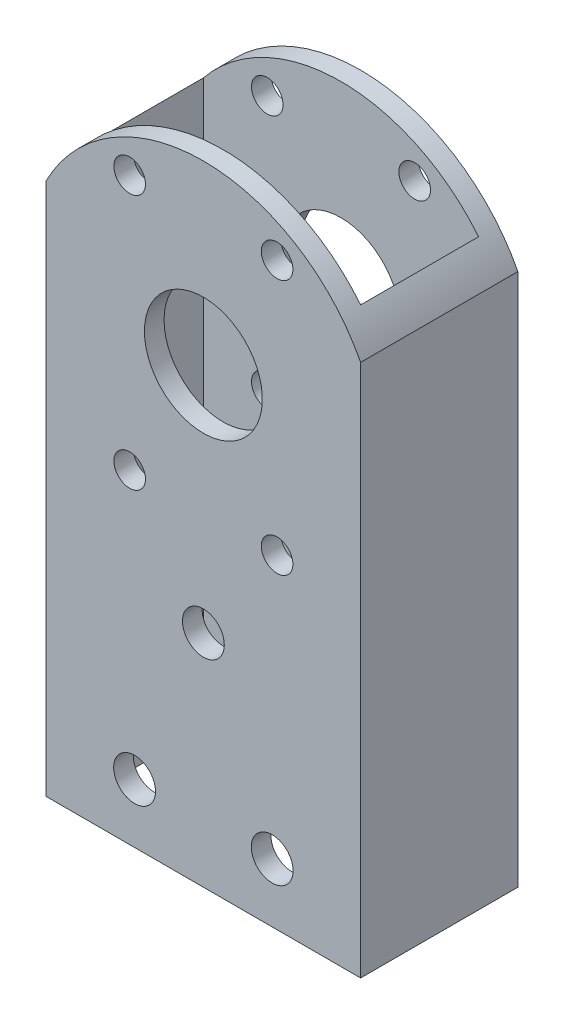
SolidWorks part; units mm, degrees
material "6061-T6 (SS)"
ref_plane "Front" through (0, 0, 0) normal (0, 0, 1) x (1, 0, 0)
ref_plane "Top" through (0, 0, 0) normal (0, 1, 0) x (1, 0, 0)
ref_plane "Right" through (0, 0, 0) normal (1, 0, 0) x (0, 0, -1)
sketch "Sketch1" plane through (0, 0, 0) normal (0, 1, 0) x (1, 0, 0)
  line L1 (-25.4, -12.7) -> (25.4, -12.7)
  line L2 (-25.4, -12.7) -> (-25.4, 12.7)
  line L3 (-25.4, 12.7) -> (25.4, 12.7)
  line L4 (25.4, -12.7) -> (25.4, 12.7)
  line L5 (-25.4, -12.7) -> (25.4, 12.7) construction
  line L6 (-25.4, 12.7) -> (25.4, -12.7) construction
  point P0 (0, 0)
  dimension "D1" = 25.4
  dimension "D2" = 50.8
extrude "Extrude-Thin1" add sketch "Sketch1" along normal blind 101.6 thin thin type one direction reverse wall 3.175
sketch "Sketch2" plane through (0, 0, -12.7) normal (0, 0, -1) x (-1, 0, 0)
  line L0 (0, 101.6) -> (0, 69.85)
  line L1 (-25.4, 101.6) -> (25.4, 101.6) construction
  line L3 (0, 60.325) -> (0, 79.375) construction
  circle A1 centre (0, 69.85) radius 23.8125
  circle A3 centre (0, 69.85) radius 9.525
  point P12 (0, 69.85)
  dimension "D1" = 19.05
  dimension "D3" = 47.625
  dimension "D2" = 31.75
hole_wizard "#10 Clearance Hole1" positions "Sketch5" profile "Sketch6" hole size "#10" standard "ANSI Inch" end condition through all
sketch "Sketch5" plane through (0, 0, -12.7) normal (0, 0, -1) x (-1, 0, 0)
  line L0 (0, 101.6) -> (0, 73.025)
  line L1 (-25.4, 101.6) -> (25.4, 101.6) construction
  line L3 (-11.9063, 93.6472) -> (11.9063, 93.6472)
  line L4 (-11.9063, 93.6472) -> (-11.9063, 52.4028)
  line L5 (-11.9063, 52.4028) -> (11.9063, 52.4028)
  line L6 (11.9063, 93.6472) -> (11.9063, 52.4028)
  circle A0 centre (0, 73.025) radius 23.8125
  point P21 (-11.9063, 93.6472)
  point P22 (11.9063, 93.6472)
  point P24 (11.9063, 52.4028)
  point P25 (-11.9063, 52.4028)
  dimension "D1" = 47.625
  dimension "D2" = 28.575
  dimension "D3" = 23.8125
sketch "Sketch6" plane through (11.9063, 52.4028, -12.7) normal (1, 0, 0) x (0, 1, 0)
  line L0 (0, 0) -> (0, 25.4)
  line L1 (0, 25.4) -> (2.5527, 25.4)
  line L2 (2.5527, 25.4) -> (2.5527, 0)
  line L5 (2.5527, 0) -> (0, 0)
  line L11 (0, -6.35) -> (0, 107.95) construction
  dimension "Thru Hole Dia." = 5.1054
  dimension "Thru Hole Depth" = 25.4
sketch "Sketch7" plane through (0, 0, -12.7) normal (0, 0, -1) x (-1, 0, 0)
  line L0 (-11.9063, 93.6472) -> (11.9063, 52.4028) construction
  circle A1 centre (0, 73.025) radius 9.525
  point P9 (0, 73.025)
  dimension "D1" = 19.05
extrude "Cut-Extrude2" cut sketch "Sketch7" against normal through all both
hole_wizard "1/4 Clearance Hole2" positions "Sketch8" profile "Sketch9" hole size "1/4" standard "ANSI Inch" end condition through all
sketch "Sketch8" plane through (0, 0, 12.7) normal (0, 0, 1) x (1, 0, 0)
  line L2 (-25.4, 101.6) -> (-25.4, 0) construction
  line L4 (-25.4, 0) -> (25.4, 0) construction
  point P0 (-11.1125, 9.525)
  point P2 (11.1125, 9.525)
  point P14 (-109.1715, 68.7854)
  dimension "D1" = 22.225
  dimension "D2" = 14.2875
  dimension "D3" = 9.525
sketch "Sketch9" plane through (-11.1125, 9.525, 12.7) normal (1, 0, 0) x (0, -1, 0)
  line L0 (0, 0) -> (0, 25.4)
  line L1 (0, 25.4) -> (3.3782, 25.4)
  line L2 (3.3782, 25.4) -> (3.3782, 0)
  line L5 (3.3782, 0) -> (0, 0)
  line L11 (0, -6.35) -> (0, 107.95) construction
  dimension "Thru Hole Dia." = 6.7564
  dimension "Thru Hole Depth" = 25.4
sketch "Sketch10" plane through (0, 0, -12.7) normal (0, 0, -1) x (-1, 0, 0)
  line L0 (-25.4, 86.1159) -> (-25.4, 101.6)
  line L1 (-25.4, 101.6) -> (25.4, 101.6)
  line L2 (25.4, 101.6) -> (25.4, 86.1159)
  line L3 (25.4, 101.6) -> (25.4, 0) construction
  arc A0 (25.4, 86.1159) -> (-25.4, 86.1159) centre (0, 73.025) ccw
  line M13 (25.4, 0) -> (25.4, 101.6)
  line M14 (25.4, 101.6) -> (-25.4, 101.6)
  line M15 (-25.4, 101.6) -> (-25.4, 0)
extrude "Cut-Extrude3" cut sketch "Sketch10" against normal through all contours A0 L1 M15 | A0 M13 M14 region at (-19.4433, 97.2944, -12.7) region at (19.4433, 97.2944, -12.7)
sketch "Sketch13" plane through (0, 0, 12.7) normal (0, 0, 1) x (1, 0, 0)
  line L4 (-25.4, 86.1159) -> (-25.4, 0) construction
  point P0 (0, 35.56)
  dimension "D1" = 35.56
  dimension "D2" = 25.4
hole_wizard "1/4 Clearance Hole1" positions "Sketch13" profile "Sketch12" hole size "1/4" standard "ANSI Inch" end condition through all
sketch "Sketch12" plane through (0, 35.56, 12.7) normal (1, 0, 0) x (0, -1, 0)
  line L0 (0, 0) -> (0, 25.4)
  line L1 (0, 25.4) -> (3.3782, 25.4)
  line L2 (3.3782, 25.4) -> (3.3782, 0)
  line L5 (3.3782, 0) -> (0, 0)
  line L11 (0, -6.35) -> (0, 107.95) construction
  dimension "Thru Hole Dia." = 6.7564
  dimension "Thru Hole Depth" = 25.4
